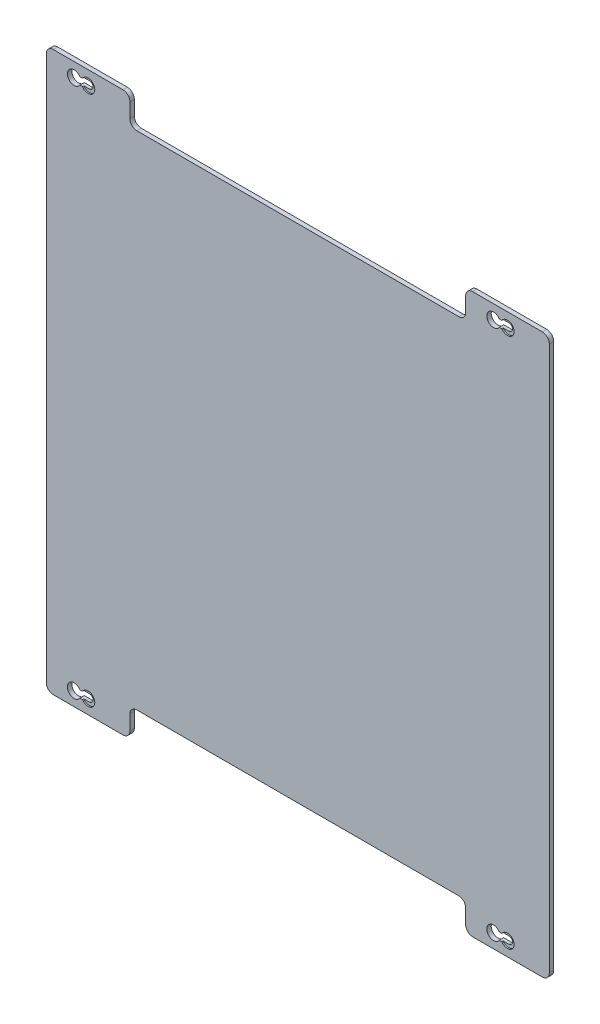
SolidWorks part; units mm, degrees
ref_plane "Front Plane" through (0, 0, 0) normal (0, 0, 1) x (1, 0, 0)
ref_plane "Top Plane" through (0, 0, 0) normal (0, 1, 0) x (1, 0, 0)
ref_plane "Right Plane" through (0, 0, 0) normal (1, 0, 0) x (0, 0, -1)
sketch "Model" plane through (0, 0, 0) normal (0, 0, 1) x (1, 0, 0)
  line L0 (175.5, 200.5049) -> (125.5, 200.5049)
  line L1 (144.6008, 187.9152) -> (150.5, 187.9152)
  line L2 (-175.5, 200.5049) -> (-125.5, 200.5049)
  line L3 (-115.5, 180) -> (115.5, 180)
  line L4 (-120.5, 185) -> (-120.5, 195.5049)
  line L5 (150.5, 193.0945) -> (144.6008, 193.0945)
  line L6 (150.5, -187.9055) -> (144.6008, -187.9055)
  line L7 (-180.5, -195.5049) -> (-180.5, 195.5049)
  line L8 (-120.5, -185) -> (-120.5, -195.5049)
  line L9 (-175.5, -200.5049) -> (-125.5, -200.5049)
  line L10 (-115.5, -180) -> (115.5, -180)
  line L11 (144.6008, -193.0848) -> (150.5, -193.0848)
  line L12 (-150.5, -187.9055) -> (-156.3992, -187.9055)
  line L13 (-156.3992, -193.0848) -> (-150.5, -193.0848)
  line L15 (120.5, 185) -> (120.5, 195.5049)
  line L16 (120.5, -185) -> (120.5, -195.5049)
  line L17 (175.5, -200.5049) -> (125.5, -200.5049)
  line L23 (180.5, 195.5049) -> (180.5, -195.5049)
  line L1211 (-150.5, 193.0945) -> (-156.3992, 193.0945)
  line L1300 (-156.3992, 187.9152) -> (-150.5, 187.9152)
  arc A0 (120.5, -195.5049) -> (125.5, -200.5049) centre (125.5, -195.5049) ccw
  arc A1 (175.5, -200.5049) -> (180.5, -195.5049) centre (175.5, -195.5049) ccw
  arc A2 (180.5, 195.5049) -> (175.5, 200.5049) centre (175.5, 195.5049) ccw
  arc A3 (120.5, 195.5049) -> (125.5, 200.5049) centre (125.5, 195.5049) cw
  arc A4 (120.5, 185) -> (115.5, 180) centre (115.5, 185) cw
  arc A5 (-120.5, 185) -> (-115.5, 180) centre (-115.5, 185) ccw
  arc A6 (-125.5, -200.5049) -> (-120.5, -195.5049) centre (-125.5, -195.5049) ccw
  arc A7 (-115.5, -180) -> (-120.5, -185) centre (-115.5, -185) ccw
  arc A8 (-180.5, -195.5049) -> (-175.5, -200.5049) centre (-175.5, -195.5049) ccw
  arc A9 (-120.5, 195.5049) -> (-125.5, 200.5049) centre (-125.5, 195.5049) ccw
  arc A10 (-175.5, 200.5049) -> (-180.5, 195.5049) centre (-175.5, 195.5049) ccw
  arc A11 (-150.5, 187.9152) -> (-150.5, 193.0945) centre (-150.5, 190.5049) ccw
  arc A12 (120.5, -185) -> (115.5, -180) centre (115.5, -185) ccw
  arc A13 (144.6008, 193.0945) -> (144.6008, 187.9152) centre (140.5, 190.5049) ccw
  arc A14 (150.5, 187.9152) -> (150.5, 193.0945) centre (150.5, 190.5049) ccw
  arc A15 (146.3992, 187.9152) -> (146.3992, 193.0945) centre (150.5, 190.5049) ccw construction
  arc A16 (144.6008, -187.9055) -> (144.6008, -193.0848) centre (140.5, -190.4951) ccw
  arc A17 (146.3992, -193.0848) -> (146.3992, -187.9055) centre (150.5, -190.4951) ccw construction
  arc A18 (150.5, -193.0848) -> (150.5, -187.9055) centre (150.5, -190.4951) ccw
  arc A19 (-154.6008, -193.0848) -> (-154.6008, -187.9055) centre (-150.5, -190.4951) ccw construction
  arc A20 (-150.5, -193.0848) -> (-150.5, -187.9055) centre (-150.5, -190.4951) ccw
  arc A21 (-156.3992, -187.9055) -> (-156.3992, -193.0848) centre (-160.5, -190.4951) ccw
  arc A31 (-154.6008, 187.9152) -> (-154.6008, 193.0945) centre (-150.5, 190.5049) ccw construction
  arc A32 (-156.3992, 193.0945) -> (-156.3992, 187.9152) centre (-160.5, 190.5049) ccw
  dimension "D1" = 360
  dimension "D11" = 5
  dimension "D12" = 4.85
  dimension "D13" = 4.85
  dimension "D17" = 5
  dimension "D18" = 5
  dimension "D19" = 5
  dimension "D20" = 5
  dimension "D21" = 5
  dimension "D22" = 5
  dimension "D23" = 5
  dimension "D24" = 5
  dimension "D25" = 5
  dimension "D26" = 5
  dimension "D27" = 5
  dimension "D29" = 10
  dimension "D31" = 20
  dimension "D2" = 180
  dimension "D3" = 361
  dimension "D4" = 180.5
  dimension "D5" = 60
  dimension "D6" = 60
  dimension "D7" = 20.5049
  dimension "D8" = 20.5049
  dimension "D9" = 20.5049
  dimension "D10" = 20.5049
  dimension "D14" = 10
  dimension "D15" = 60
  dimension "D16" = 60
  dimension "D28" = 10
  dimension "D30" = 5.1793
  dimension "D32" = 2
  dimension "D33" = 2
extrude "Boss-Extrude1" add sketch "Model" along normal blind 3.175
sketch "Sketch2" plane through (0, 0, 3.175) normal (0, 0, 1) x (1, 0, 0)
  circle A0 centre (-150.5, 190.5049) radius 4.8
  circle A1 centre (150.5, 190.5049) radius 4.8
  circle A2 centre (150.5, -190.4951) radius 4.8
  circle A3 centre (-150.5, -190.4951) radius 4.8
  dimension "D1" = 9.6
extrude "Cut-Extrude1" cut sketch "Sketch2" against normal blind 1
sketch "Sketch3" plane through (0, 0, 3.175) normal (0, 0, 1) x (1, 0, 0)
  line L0 (-15, 162.5) -> (15, 162.5)
  line L1 (-150, -150) -> (150, -150) construction
  line L2 (-150, -150) -> (-150, 150) construction
  line L3 (-150, 150) -> (150, 150) construction
  line L4 (150, -150) -> (150, 150) construction
  line L5 (-150, -150) -> (150, 150) construction
  line L6 (-150, 150) -> (150, -150) construction
  line L7 (-15, 172.025) -> (15, 172.025)
  line L8 (35, 172.025) -> (65, 172.025)
  line L9 (35, 162.5) -> (65, 162.5)
  line L10 (85, 172.025) -> (115, 172.025)
  line L11 (85, 162.5) -> (115, 162.5)
  line L14 (-65, 172.025) -> (-35, 172.025)
  line L15 (-65, 162.5) -> (-35, 162.5)
  line L16 (-115, 172.025) -> (-85, 172.025)
  line L17 (-115, 162.5) -> (-85, 162.5)
  line L20 (-180.5, 0) -> (180.5, 0) construction
  line L21 (-180.5, 195.5049) -> (-180.5, -195.5049) construction
  line L22 (180.5, -195.5049) -> (180.5, 195.5049) construction
  line L25 (-115, -162.5) -> (-85, -162.5)
  line L26 (-115, -172.025) -> (-85, -172.025)
  line L27 (-65, -162.5) -> (-35, -162.5)
  line L28 (-65, -172.025) -> (-35, -172.025)
  line L31 (85, -162.5) -> (115, -162.5)
  line L32 (85, -172.025) -> (115, -172.025)
  line L33 (35, -162.5) -> (65, -162.5)
  line L34 (35, -172.025) -> (65, -172.025)
  line L35 (-15, -172.025) -> (15, -172.025)
  line L36 (-15, -162.5) -> (15, -162.5)
  arc A0 (15, 172.025) -> (15, 162.5) centre (15, 167.2625) cw
  arc A1 (-15, 162.5) -> (-15, 172.025) centre (-15, 167.2625) cw
  arc A2 (35, 162.5) -> (35, 172.025) centre (35, 167.2625) cw
  arc A3 (65, 172.025) -> (65, 162.5) centre (65, 167.2625) cw
  arc A4 (85, 162.5) -> (85, 172.025) centre (85, 167.2625) cw
  arc A5 (115, 172.025) -> (115, 162.5) centre (115, 167.2625) cw
  arc A8 (-65, 162.5) -> (-65, 172.025) centre (-65, 167.2625) cw
  arc A9 (-35, 172.025) -> (-35, 162.5) centre (-35, 167.2625) cw
  arc A10 (-115, 162.5) -> (-115, 172.025) centre (-115, 167.2625) cw
  arc A11 (-85, 172.025) -> (-85, 162.5) centre (-85, 167.2625) cw
  arc A16 (-85, -172.025) -> (-85, -162.5) centre (-85, -167.2625) ccw
  arc A17 (-115, -162.5) -> (-115, -172.025) centre (-115, -167.2625) ccw
  arc A18 (-35, -172.025) -> (-35, -162.5) centre (-35, -167.2625) ccw
  arc A19 (-65, -162.5) -> (-65, -172.025) centre (-65, -167.2625) ccw
  arc A22 (115, -172.025) -> (115, -162.5) centre (115, -167.2625) ccw
  arc A23 (85, -162.5) -> (85, -172.025) centre (85, -167.2625) ccw
  arc A24 (65, -172.025) -> (65, -162.5) centre (65, -167.2625) ccw
  arc A25 (35, -162.5) -> (35, -172.025) centre (35, -167.2625) ccw
  arc A26 (-15, -162.5) -> (-15, -172.025) centre (-15, -167.2625) ccw
  arc A27 (15, -172.025) -> (15, -162.5) centre (15, -167.2625) ccw
  point P0 (0, 0)
  point P12 (0, 162.5)
  dimension "D3" = 4.7625
  dimension "D4" = 30
  dimension "D1" = 300
  dimension "D2" = 300
  dimension "D5" = 25
  dimension "D6" = 3
  dimension "D7" = 3
extrude "Cut-Extrude2" [suppressed] cut sketch "Sketch3" against normal up to surface (3.175 mm away) up to face at (-155.0399, 190.5049, 0)
